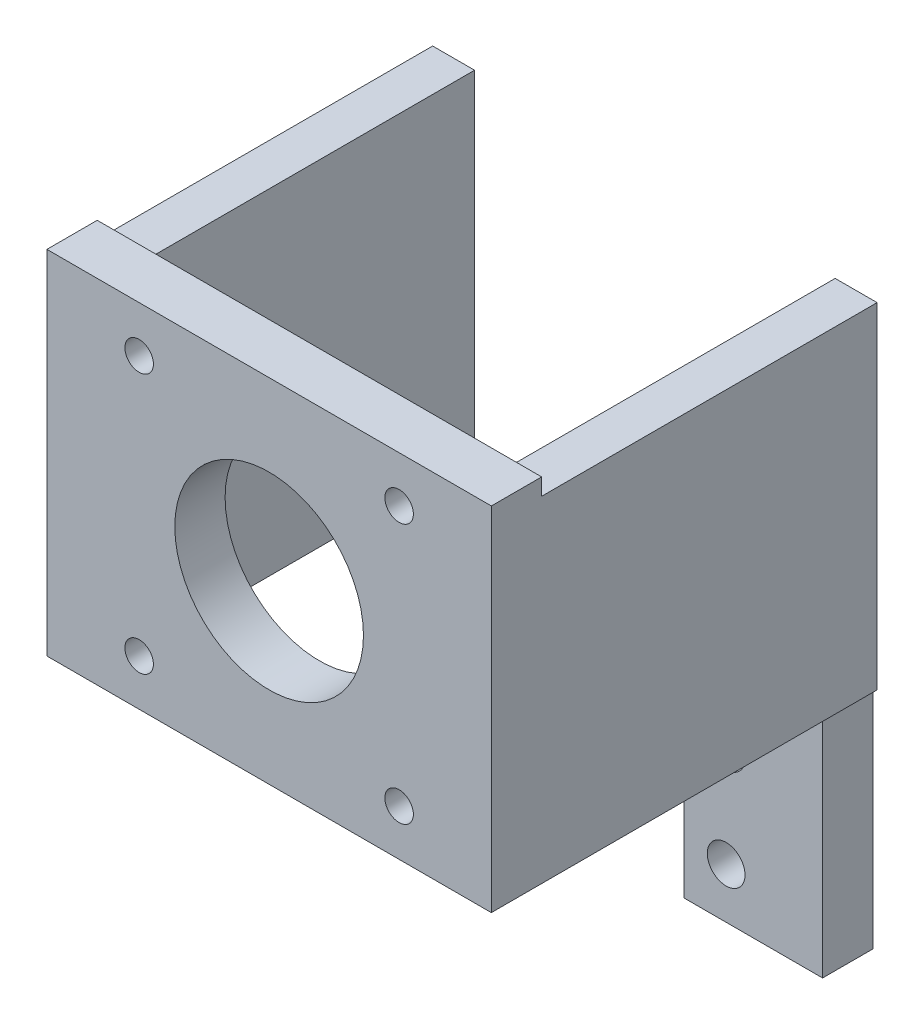
SolidWorks part; units mm, degrees
ref_plane "Спереди" through (0, 0, 0) normal (0, 0, 1) x (1, 0, 0)
ref_plane "Сверху" through (0, 0, 0) normal (0, 1, 0) x (1, 0, 0)
ref_plane "Справа" through (0, 0, 0) normal (1, 0, 0) x (0, 0, -1)
other "Configuration Table"
sketch "Фланец_эскиз" plane through (0, 0, 0) normal (0, 0, 1) x (1, 0, 0)
  line L0 (-26.5, -21) -> (26.5, -21)
  line L1 (26.5, -21) -> (26.5, 21)
  line L2 (26.5, 21) -> (-26.5, 21)
  line L3 (-26.5, 21) -> (-26.5, -21)
  dimension "D1" = 26.5
  dimension "D2" = 21
  dimension "D3" = 26.5
  dimension "D4" = 21
  dimension "D5" = 26.5
  dimension "D6" = 21
  dimension "D7" = 26.5
  dimension "D8" = 21
extrude "Передняя_пластина" add sketch "Фланец_эскиз" along normal blind 6 from offset 40
sketch "Скоба_эскиз" plane through (0, 0, 0) normal (0, 0, 1) x (1, 0, 0)
  line L0 (-26.5, -21) -> (-21.5, -21)
  line L1 (-21.5, -21) -> (-21.5, 19)
  line L2 (-21.5, 19) -> (-26.5, 19)
  line L3 (-26.5, 19) -> (-26.5, -21)
  line L4 (21.5, -21) -> (26.5, -21)
  line L5 (26.5, -21) -> (26.5, 19)
  line L6 (26.5, 19) -> (21.5, 19)
  line L7 (21.5, 19) -> (21.5, -21)
  dimension "D1" = 26.5
  dimension "D2" = 21
  dimension "D4" = 21
  dimension "D7" = 26.5
  dimension "D3" = 21.5
  dimension "D5" = 21.5
  dimension "D6" = 19
  dimension "D8" = 19
  dimension "D9" = 21.5
  dimension "D10" = 21
  dimension "D11" = 26.5
  dimension "D12" = 21
  dimension "D13" = 26.5
  dimension "D14" = 19
  dimension "D15" = 21.5
  dimension "D16" = 19
extrude "Боковины" add sketch "Скоба_эскиз" along normal blind 40
sketch "Лапки_эскиз" plane through (0, 0, 0) normal (0, 0, 1) x (1, 0, 0)
  line L0 (-21.5, -18) -> (-26.5, -18)
  line L1 (-26.5, -18) -> (-26.5, -21)
  line L2 (-26.5, -21) -> (-26, -21)
  line L3 (-26, -21) -> (-26, -48)
  line L4 (-26, -48) -> (-9.5, -48)
  line L5 (-9.5, -48) -> (-9.5, -21)
  line L6 (-9.5, -21) -> (-21.5, -21)
  line L7 (-21.5, -21) -> (-21.5, -18)
  line L8 (21.5, -18) -> (26.5, -18)
  line L9 (26.5, -18) -> (26.5, -21)
  line L10 (26.5, -21) -> (26, -21)
  line L11 (26, -21) -> (26, -48)
  line L12 (26, -48) -> (9.5, -48)
  line L13 (9.5, -48) -> (9.5, -21)
  line L14 (9.5, -21) -> (21.5, -21)
  line L15 (21.5, -21) -> (21.5, -18)
  dimension "D3" = 26.5
  dimension "D5" = 26.5
  dimension "D6" = 21
  dimension "D8" = 21
  dimension "D15" = 21.5
  dimension "D1" = 21.5
  dimension "D2" = 18
  dimension "D4" = 18
  dimension "D9" = 26
  dimension "D10" = 48
  dimension "D11" = 9.5
  dimension "D12" = 48
  dimension "D13" = 9.5
  dimension "D14" = 21
  dimension "D16" = 21
  dimension "D17" = 21.5
  dimension "D18" = 18
  dimension "D19" = 26.5
  dimension "D20" = 18
  dimension "D21" = 26.5
  dimension "D22" = 21
  dimension "D23" = 26
  dimension "D24" = 21
  dimension "D25" = 26
  dimension "D26" = 48
  dimension "D27" = 9.5
  dimension "D28" = 48
  dimension "D29" = 9.5
  dimension "D30" = 21
  dimension "D31" = 21.5
  dimension "D32" = 21
extrude "Лапки_основания" add sketch "Лапки_эскиз" along normal blind 6
sketch "Крепёж_фланца_эскиз" plane through (0, 0, 0) normal (0, 0, 1) x (1, 0, 0)
  circle A0 centre (0, 0) radius 11.25
  circle A1 centre (-15.5, -15.5) radius 1.7
  circle A2 centre (-15.5, 15.5) radius 1.7
  circle A3 centre (15.5, -15.5) radius 1.7
  circle A4 centre (15.5, 15.5) radius 1.7
  dimension "D1" = 22.5
  dimension "D4" = 3.4
  dimension "D7" = 3.4
  dimension "D10" = 3.4
  dimension "D13" = 3.4
  dimension "D2" = 15.5
  dimension "D3" = 15.5
  dimension "D5" = 15.5
  dimension "D6" = 15.5
  dimension "D8" = 15.5
  dimension "D9" = 15.5
  dimension "D11" = 15.5
  dimension "D12" = 15.5
extrude "Отверстия_фланца" cut sketch "Крепёж_фланца_эскиз" against normal through all and the other way through all
sketch "Крепёж_основания_эскиз" plane through (0, 0, 0) normal (0, 0, 1) x (1, 0, 0)
  circle A0 centre (-14.5, -30) radius 2.25
  circle A1 centre (-14.5, -42) radius 2.25
  circle A2 centre (14.5, -30) radius 2.25
  circle A3 centre (14.5, -42) radius 2.25
  dimension "D3" = 4.5
  dimension "D6" = 4.5
  dimension "D9" = 4.5
  dimension "D12" = 4.5
  dimension "D1" = 14.5
  dimension "D2" = 30
  dimension "D4" = 14.5
  dimension "D5" = 42
  dimension "D7" = 14.5
  dimension "D8" = 30
  dimension "D10" = 14.5
  dimension "D11" = 42
extrude "Отверстия_основания" cut sketch "Крепёж_основания_эскиз" against normal through all and the other way through all
equation "\"Z корпус\" = 42"
equation "\"Z длина мотора\" = 40"
equation "\"Z зазор\" = 0.5"
equation "\"Z стенка\" = 5"
equation "\"Z пластина\" = 6"
equation "\"Z отступ от края\" = 2"
equation "\"Z лапка\" = 6"
equation "\"Z ширина лапки\" = 10"
equation "\"Z центр лапки\" = 14.5"
equation "\"Z задняя граница\" = 48"
equation "\"Z перекрытие\" = 3"
equation "\"Z шаг М3\" = 31"
equation "\"Z отверстие М3\" = 3.4"
equation "\"Z буртик\" = 22.5"
equation "\"Z отверстие М4\" = 4.5"
equation "\"Z первый ряд М4\" = 30"
equation "\"Z шаг М4\" = 12"
equation "\"D1@Фланец_эскиз\" = \"Z корпус\"/2+\"Z зазор\"+\"Z стенка\""
equation "\"D2@Фланец_эскиз\" = \"Z корпус\"/2"
equation "\"D3@Фланец_эскиз\" = \"Z корпус\"/2+\"Z зазор\"+\"Z стенка\""
equation "\"D6@Фланец_эскиз\" = \"Z корпус\"/2"
equation "\"D1@Передняя_пластина\" = \"Z пластина\""
equation "\"D19@Передняя_пластина\" = \"Z длина мотора\""
equation "\"D1@Скоба_эскиз\" = \"Z корпус\"/2+\"Z зазор\"+\"Z стенка\""
equation "\"D2@Скоба_эскиз\" = \"Z корпус\"/2"
equation "\"D3@Скоба_эскиз\" = \"Z корпус\"/2+\"Z зазор\""
equation "\"D6@Скоба_эскиз\" = \"Z корпус\"/2-\"Z отступ от края\""
equation "\"D9@Скоба_эскиз\" = \"Z корпус\"/2+\"Z зазор\""
equation "\"D10@Скоба_эскиз\" = \"Z корпус\"/2"
equation "\"D11@Скоба_эскиз\" = \"Z корпус\"/2+\"Z зазор\"+\"Z стенка\""
equation "\"D14@Скоба_эскиз\" = \"Z корпус\"/2-\"Z отступ от края\""
equation "\"D1@Боковины\" = \"Z длина мотора\""
equation "\"D1@Лапки_эскиз\" = \"Z корпус\"/2+\"Z зазор\""
equation "\"D2@Лапки_эскиз\" = \"Z корпус\"/2-\"Z перекрытие\""
equation "\"D3@Лапки_эскиз\" = \"Z корпус\"/2+\"Z зазор\"+\"Z стенка\""
equation "\"D6@Лапки_эскиз\" = \"Z корпус\"/2"
equation "\"D7@Лапки_эскиз\" = \"Z корпус\"/2+\"Z зазор\"+\"Z стенка\"-0.5"
equation "\"D10@Лапки_эскиз\" = \"Z задняя граница\""
equation "\"D11@Лапки_эскиз\" = \"Z центр лапки\"-\"Z ширина лапки\"/2"
equation "\"D14@Лапки_эскиз\" = \"Z корпус\"/2"
equation "\"D17@Лапки_эскиз\" = \"Z корпус\"/2+\"Z зазор\""
equation "\"D18@Лапки_эскиз\" = \"Z корпус\"/2-\"Z перекрытие\""
equation "\"D19@Лапки_эскиз\" = \"Z корпус\"/2+\"Z зазор\"+\"Z стенка\""
equation "\"D22@Лапки_эскиз\" = \"Z корпус\"/2"
equation "\"D23@Лапки_эскиз\" = \"Z корпус\"/2+\"Z зазор\"+\"Z стенка\"-0.5"
equation "\"D26@Лапки_эскиз\" = \"Z задняя граница\""
equation "\"D27@Лапки_эскиз\" = \"Z центр лапки\"-\"Z ширина лапки\"/2"
equation "\"D30@Лапки_эскиз\" = \"Z корпус\"/2"
equation "\"D1@Лапки_основания\" = \"Z лапка\""
equation "\"D1@Крепёж_фланца_эскиз\" = \"Z буртик\""
equation "\"D2@Крепёж_фланца_эскиз\" = \"Z шаг М3\"/2"
equation "\"D3@Крепёж_фланца_эскиз\" = \"Z шаг М3\"/2"
equation "\"D4@Крепёж_фланца_эскиз\" = \"Z отверстие М3\""
equation "\"D5@Крепёж_фланца_эскиз\" = \"Z шаг М3\"/2"
equation "\"D6@Крепёж_фланца_эскиз\" = \"Z шаг М3\"/2"
equation "\"D7@Крепёж_фланца_эскиз\" = \"Z отверстие М3\""
equation "\"D8@Крепёж_фланца_эскиз\" = \"Z шаг М3\"/2"
equation "\"D9@Крепёж_фланца_эскиз\" = \"Z шаг М3\"/2"
equation "\"D10@Крепёж_фланца_эскиз\" = \"Z отверстие М3\""
equation "\"D11@Крепёж_фланца_эскиз\" = \"Z шаг М3\"/2"
equation "\"D12@Крепёж_фланца_эскиз\" = \"Z шаг М3\"/2"
equation "\"D13@Крепёж_фланца_эскиз\" = \"Z отверстие М3\""
equation "\"D1@Крепёж_основания_эскиз\" = \"Z центр лапки\""
equation "\"D2@Крепёж_основания_эскиз\" = \"Z первый ряд М4\""
equation "\"D3@Крепёж_основания_эскиз\" = \"Z отверстие М4\""
equation "\"D4@Крепёж_основания_эскиз\" = \"Z центр лапки\""
equation "\"D5@Крепёж_основания_эскиз\" = \"Z первый ряд М4\"+\"Z шаг М4\""
equation "\"D6@Крепёж_основания_эскиз\" = \"Z отверстие М4\""
equation "\"D7@Крепёж_основания_эскиз\" = \"Z центр лапки\""
equation "\"D8@Крепёж_основания_эскиз\" = \"Z первый ряд М4\""
equation "\"D9@Крепёж_основания_эскиз\" = \"Z отверстие М4\""
equation "\"D10@Крепёж_основания_эскиз\" = \"Z центр лапки\""
equation "\"D11@Крепёж_основания_эскиз\" = \"Z первый ряд М4\"+\"Z шаг М4\""
equation "\"D12@Крепёж_основания_эскиз\" = \"Z отверстие М4\""
